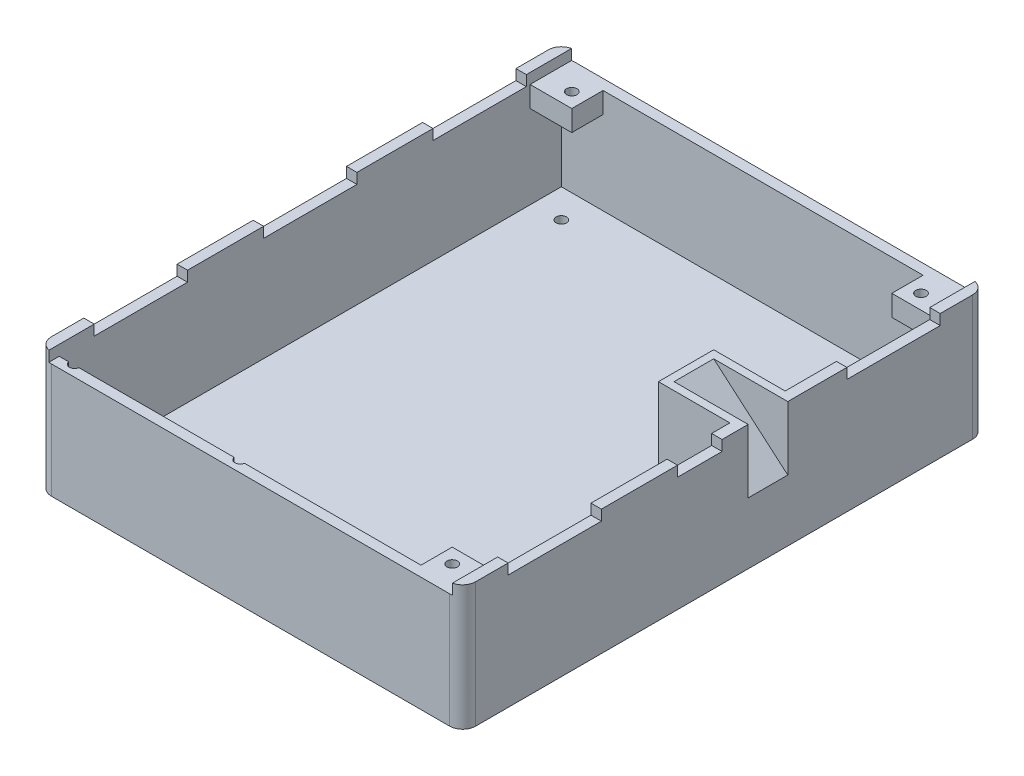
SolidWorks part; units mm, degrees
ref_plane "Front Plane" through (0, 0, 0) normal (0, 0, 1) x (1, 0, 0)
ref_plane "Top Plane" through (0, 0, 0) normal (0, 1, 0) x (1, 0, 0)
ref_plane "Right Plane" through (0, 0, 0) normal (1, 0, 0) x (0, 0, -1)
sketch "Sketch1" plane through (0, 95.465, 0) normal (0, 1, 0) x (1, 0, 0)
  line L9 (159.9807, -123.0664) -> (159.9807, -100.3704) construction
  line L13 (159.9807, -65.3704) -> (159.9807, -47.9349) construction
  line L26 (5.9807, -65.3704) -> (1.9807, -65.3704) construction
  line L27 (1.9807, -65.3704) -> (1.9807, -100.3704) construction
  line L28 (1.9807, -100.3704) -> (5.9807, -100.3704) construction
  line L30 (5.9807, -130.3704) -> (1.9807, -130.3704) construction
  line L31 (1.9807, -130.3704) -> (1.9807, -165.3704) construction
  line L32 (1.9807, -165.3704) -> (5.9807, -165.3704) construction
  line L34 (5.9807, -195.3704) -> (1.9807, -195.3704) construction
  line L35 (1.9807, -195.3704) -> (1.9807, -230.3704) construction
  line L36 (1.9807, -230.3704) -> (5.9807, -230.3704) construction
  line L38 (5.9807, -247.8059) -> (159.9807, -247.8059) construction
  line L39 (159.9807, -247.8059) -> (159.9807, -230.3704) construction
  line L43 (159.9807, -195.3704) -> (159.9807, -165.3704) construction
  line L47 (5.9807, -130.3704) -> (5.9807, -100.3704) construction
  line L48 (5.9807, -195.3704) -> (5.9807, -165.3704) construction
  line L49 (5.9807, -247.8059) -> (5.9807, -230.3704) construction
  line L50 (163.9807, -195.3704) -> (163.9807, -230.3704) construction
  line L51 (163.9807, -149.0664) -> (163.9807, -165.3704) construction
  line L52 (159.9807, -139.0664) -> (159.9807, -149.0664) construction
  line L53 (135.9622, -139.0664) -> (159.9807, -139.0664) construction
  line L54 (135.9622, -123.0664) -> (135.9622, -139.0664) construction
  line L55 (159.9807, -123.0664) -> (135.9622, -123.0664) construction
  line L56 (163.9807, -100.3704) -> (159.9807, -100.3704) construction
  line L57 (159.9807, -65.3704) -> (163.9807, -65.3704) construction
  line L58 (163.9807, -65.3704) -> (163.9807, -100.3704) construction
  line L59 (130.9016, -47.9349) -> (159.9807, -47.9349) construction
  line L60 (5.9807, -47.9349) -> (118.5112, -47.9349) construction
  line L61 (5.9807, -65.3704) -> (5.9807, -47.9349) construction
  line L62 (5.9807, -130.3704) -> (1.9807, -130.3704)
  line L63 (5.9807, -130.3704) -> (5.9807, -100.3704)
  line L64 (1.9807, -100.3704) -> (5.9807, -100.3704)
  line L65 (1.9807, -130.3704) -> (1.9807, -165.3704)
  line L66 (1.9807, -165.3704) -> (5.9807, -165.3704)
  line L67 (5.9807, -195.3704) -> (5.9807, -165.3704)
  line L68 (5.9807, -195.3704) -> (1.9807, -195.3704)
  line L69 (1.9807, -195.3704) -> (1.9807, -230.3704)
  line L70 (1.9807, -230.3704) -> (5.9807, -230.3704)
  line L71 (5.9807, -247.8059) -> (5.9807, -230.3704)
  line L72 (5.9807, -247.8059) -> (159.9807, -247.8059)
  line L73 (159.9807, -247.8059) -> (159.9807, -230.3704)
  line L74 (163.9807, -195.3704) -> (163.9807, -230.3704)
  line L75 (159.9807, -195.3704) -> (159.9807, -165.3704)
  line L76 (163.9807, -149.0664) -> (163.9807, -165.3704)
  line L77 (159.9807, -139.0664) -> (159.9807, -149.0664)
  line L78 (135.9622, -139.0664) -> (159.9807, -139.0664)
  line L79 (135.9622, -123.0664) -> (135.9622, -139.0664)
  line L80 (159.9807, -123.0664) -> (135.9622, -123.0664)
  line L81 (159.9807, -123.0664) -> (159.9807, -100.3704)
  line L82 (163.9807, -100.3704) -> (159.9807, -100.3704)
  line L83 (159.9807, -65.3704) -> (163.9807, -65.3704)
  line L84 (163.9807, -65.3704) -> (163.9807, -100.3704)
  line L85 (159.9807, -65.3704) -> (159.9807, -47.9349)
  line L86 (130.9016, -47.9349) -> (159.9807, -47.9349)
  line L87 (5.9807, -47.9349) -> (118.5112, -47.9349)
  line L88 (5.9807, -65.3704) -> (5.9807, -47.9349)
  line L89 (5.9807, -65.3704) -> (1.9807, -65.3704)
  line L90 (1.9807, -65.3704) -> (1.9807, -100.3704)
  line L91 (163.9807, -230.3704) -> (159.9807, -230.3704) construction
  line L92 (159.9807, -195.3704) -> (163.9807, -195.3704) construction
  line L93 (163.9807, -230.3704) -> (159.9807, -230.3704)
  line L94 (159.9807, -195.3704) -> (163.9807, -195.3704)
  line L95 (163.9807, -165.3704) -> (159.9807, -165.3704) construction
  line L96 (163.9807, -165.3704) -> (159.9807, -165.3704)
  line L97 (159.9807, -149.0664) -> (163.9807, -149.0664) construction
  line L98 (159.9807, -149.0664) -> (163.9807, -149.0664)
  line L99 (5.5807, -47.5349) -> (118.5112, -47.5349)
  line L100 (5.5807, -64.9704) -> (5.5807, -47.5349)
  line L101 (5.5807, -64.9704) -> (1.5807, -64.9704)
  line L102 (1.5807, -64.9704) -> (1.5807, -100.7704)
  line L103 (1.5807, -100.7704) -> (5.5807, -100.7704)
  line L104 (5.5807, -129.9704) -> (5.5807, -100.7704)
  line L105 (5.5807, -129.9704) -> (1.5807, -129.9704)
  line L106 (1.5807, -129.9704) -> (1.5807, -165.7704)
  line L107 (1.5807, -165.7704) -> (5.5807, -165.7704)
  line L108 (5.5807, -194.9704) -> (5.5807, -165.7704)
  line L109 (5.5807, -194.9704) -> (1.5807, -194.9704)
  line L110 (1.5807, -194.9704) -> (1.5807, -230.7704)
  line L111 (1.5807, -230.7704) -> (5.5807, -230.7704)
  line L112 (5.5807, -248.2059) -> (5.5807, -230.7704)
  line L113 (5.5807, -248.2059) -> (160.3807, -248.2059)
  line L114 (160.3807, -248.2059) -> (160.3807, -230.7704)
  line L115 (164.3807, -230.7704) -> (160.3807, -230.7704)
  line L116 (164.3807, -194.9704) -> (164.3807, -230.7704)
  line L117 (160.3807, -194.9704) -> (164.3807, -194.9704)
  line L118 (160.3807, -194.9704) -> (160.3807, -165.7704)
  line L119 (164.3807, -165.7704) -> (160.3807, -165.7704)
  line L120 (164.3807, -148.6664) -> (164.3807, -165.7704)
  line L121 (160.3807, -148.6664) -> (164.3807, -148.6664)
  line L122 (160.3807, -138.6664) -> (160.3807, -148.6664)
  line L123 (136.3622, -138.6664) -> (160.3807, -138.6664)
  line L124 (136.3622, -123.4664) -> (136.3622, -138.6664)
  line L125 (160.3807, -123.4664) -> (136.3622, -123.4664)
  line L126 (160.3807, -123.4664) -> (160.3807, -100.7704)
  line L127 (164.3807, -100.7704) -> (160.3807, -100.7704)
  line L128 (164.3807, -64.9704) -> (164.3807, -100.7704)
  line L129 (160.3807, -64.9704) -> (164.3807, -64.9704)
  line L130 (160.3807, -64.9704) -> (160.3807, -47.5349)
  line L131 (130.9016, -47.5349) -> (160.3807, -47.5349)
  line L133 (164.3807, -248.2059) -> (1.5807, -248.2059)
  line L134 (164.3807, -248.2059) -> (164.3807, -47.5349)
  line L135 (164.3807, -47.5349) -> (1.5807, -47.5349)
  line L136 (1.5807, -248.2059) -> (1.5807, -47.5349)
  dimension "D1" = 0.4
extrude "Boss-Extrude2" add sketch "Sketch1" against normal blind 4 contours L136 L101 L100 L135 | L136 L105 L104 L103 | L136 L109 L108 L107 | L136 L133 L112 L111 | L133 L134 L115 L114 | L117 L134 L119 L118 | L121 L134 L127 L126 L125 L124 L123 L122 | L134 L135 L130 L129 region at (3.5807, 95.465, 56.2527) region at (162.3807, 95.465, 56.2527) region at (3.5807, 95.465, 115.3704) region at (3.5807, 95.465, 180.3704) region at (153.1929, 95.465, 128.8817) region at (3.5807, 95.465, 239.4882) region at (162.3807, 95.465, 180.3704) region at (162.3807, 95.465, 239.4882)
sketch "Sketch2" plane through (0, 95.465, 0) normal (0, 1, 0) x (1, 0, 0)
  line L1 (136.3622, -123.4664) -> (164.3807, -123.4664)
  line L2 (136.3622, -123.4664) -> (136.3622, -138.6664)
  line L3 (136.3622, -138.6664) -> (164.3807, -138.6664)
  line L4 (164.3807, -123.4664) -> (164.3807, -138.6664)
  line L8 (160.3807, -148.6664) -> (164.3807, -148.6664)
  line L9 (164.3807, -148.6664) -> (164.3807, -100.7704)
  line L10 (164.3807, -100.7704) -> (160.3807, -100.7704)
  line L11 (160.3807, -100.7704) -> (160.3807, -123.4664)
  line L12 (160.3807, -123.4664) -> (136.3622, -123.4664)
  line L13 (136.3622, -123.4664) -> (136.3622, -138.6664)
  line L14 (136.3622, -138.6664) -> (160.3807, -138.6664)
  line L15 (160.3807, -138.6664) -> (160.3807, -148.6664)
  line L16 (160.3807, -148.6664) -> (164.3807, -148.6664)
  line L17 (164.3807, -148.6664) -> (164.3807, -100.7704)
  line L18 (164.3807, -100.7704) -> (160.3807, -100.7704)
  line L19 (160.3807, -100.7704) -> (160.3807, -123.4664)
  line L20 (160.3807, -123.4664) -> (136.3622, -123.4664)
  line L21 (136.3622, -123.4664) -> (136.3622, -138.6664)
  line L22 (136.3622, -138.6664) -> (160.3807, -138.6664)
  line L23 (160.3807, -138.6664) -> (160.3807, -148.6664)
  line M10 (164.3807, -148.6664) -> (164.3807, -100.7704)
  line M13 (160.3807, -123.4664) -> (136.3622, -123.4664)
  line M14 (136.3622, -123.4664) -> (136.3622, -138.6664)
  line M15 (136.3622, -138.6664) -> (160.3807, -138.6664)
  dimension "D1" = 0
extrude "Cut-Extrude1" cut sketch "Sketch2" against normal blind 4 contours L3 L1 M15 M10 M13 M14 region at (150.3715, 95.465, 131.0664)
sketch "Sketch3" plane through (0, 91.465, 0) normal (0, -1, 0) x (1, 0, 0)
  line L0 (160.3807, 51.5349) -> (160.3807, 244.2059)
  line L1 (164.3807, 47.5349) -> (1.5807, 47.5349)
  line L2 (164.3807, 47.5349) -> (164.3807, 248.2059)
  line L3 (164.3807, 248.2059) -> (1.5807, 248.2059)
  line L4 (1.5807, 47.5349) -> (1.5807, 248.2059)
  line L5 (160.3807, 244.2059) -> (5.5807, 244.2059)
  line L6 (5.5807, 51.5349) -> (5.5807, 244.2059)
  line L7 (160.3807, 51.5349) -> (5.5807, 51.5349)
  dimension "D1" = 4
extrude "Boss-Extrude3" add sketch "Sketch3" along normal blind 40
sketch "Sketch4" plane through (0, 51.465, 0) normal (0, -1, 0) x (1, 0, 0)
  line L1 (1.5807, 47.5349) -> (164.3807, 47.5349)
  line L2 (1.5807, 47.5349) -> (1.5807, 248.2059)
  line L3 (1.5807, 248.2059) -> (164.3807, 248.2059)
  line L4 (164.3807, 47.5349) -> (164.3807, 248.2059)
extrude "Boss-Extrude4" add sketch "Sketch4" along normal blind 4
fillet "Fillet1" radius 5 1 edges at (1.5807, 71.465, 248.2059)
fillet "Fillet2" radius 5 1 edges at (164.3807, 71.465, 248.2059)
fillet "Fillet3" radius 5 1 edges at (164.3807, 71.465, 47.5349)
fillet "Fillet4" radius 5 1 edges at (1.5807, 71.465, 47.5349)
sketch "Sketch5" plane through (0, 47.465, 0) normal (0, -1, 0) x (1, 0, 0)
  line L0 (164.3807, 52.5349) -> (164.3807, 243.2059) construction
  line L1 (164.3807, 47.5349) -> (149.3807, 47.5349)
  line L2 (164.3807, 47.5349) -> (164.3807, 62.5349)
  line L3 (164.3807, 62.5349) -> (149.3807, 62.5349)
  line L4 (1.5807, 243.2059) -> (1.5807, 52.5349)
  line L5 (6.5807, 47.5349) -> (159.3807, 47.5349)
  line L6 (164.3807, 52.5349) -> (164.3807, 243.2059)
  line L7 (159.3807, 248.2059) -> (6.5807, 248.2059)
  line L8 (1.5807, 243.2059) -> (1.5807, 52.5349)
  line L9 (6.5807, 47.5349) -> (159.3807, 47.5349)
  line L10 (164.3807, 52.5349) -> (164.3807, 243.2059)
  line L11 (159.3807, 248.2059) -> (6.5807, 248.2059)
  line L12 (149.3807, 47.5349) -> (149.3807, 62.5349)
  line L13 (1.5807, 47.5349) -> (16.5807, 47.5349)
  line L14 (1.5807, 47.5349) -> (1.5807, 62.5349)
  line L15 (1.5807, 62.5349) -> (16.5807, 62.5349)
  line L16 (16.5807, 47.5349) -> (16.5807, 62.5349)
  line L17 (1.5807, 248.2059) -> (16.5807, 248.2059)
  line L18 (1.5807, 248.2059) -> (1.5807, 233.2059)
  line L19 (1.5807, 233.2059) -> (16.5807, 233.2059)
  line L20 (16.5807, 248.2059) -> (16.5807, 233.2059)
  line L21 (164.3807, 248.2059) -> (149.3807, 248.2059)
  line L22 (164.3807, 248.2059) -> (164.3807, 233.2059)
  line L23 (164.3807, 233.2059) -> (149.3807, 233.2059)
  line L24 (149.3807, 248.2059) -> (149.3807, 233.2059)
  line L25 (6.5807, 47.5349) -> (159.3807, 47.5349) construction
  line L26 (1.5807, 243.2059) -> (1.5807, 52.5349) construction
  line L27 (159.3807, 248.2059) -> (6.5807, 248.2059) construction
  circle A0 centre (149.3807, 62.5349) radius 2
  circle A1 centre (16.5807, 62.5349) radius 2
  circle A2 centre (149.3807, 233.2059) radius 2
  circle A3 centre (16.5807, 233.2059) radius 2
  arc A4 (1.5807, 52.5349) -> (6.5807, 47.5349) centre (6.5807, 52.5349) ccw
  arc A5 (159.3807, 47.5349) -> (164.3807, 52.5349) centre (159.3807, 52.5349) ccw
  arc A6 (164.3807, 243.2059) -> (159.3807, 248.2059) centre (159.3807, 243.2059) ccw
  arc A7 (6.5807, 248.2059) -> (1.5807, 243.2059) centre (6.5807, 243.2059) ccw
  arc A8 (1.5807, 52.5349) -> (6.5807, 47.5349) centre (6.5807, 52.5349) ccw
  arc A9 (159.3807, 47.5349) -> (164.3807, 52.5349) centre (159.3807, 52.5349) ccw
  arc A10 (164.3807, 243.2059) -> (159.3807, 248.2059) centre (159.3807, 243.2059) ccw
  arc A11 (6.5807, 248.2059) -> (1.5807, 243.2059) centre (6.5807, 243.2059) ccw
  dimension "D10" = 4
  dimension "D11" = 4
  dimension "D12" = 4
  dimension "D13" = 4
  dimension "D2" = 15
  dimension "D3" = 15
  dimension "D4" = 15
  dimension "D5" = 15
  dimension "D6" = 15
  dimension "D7" = 15
  dimension "D8" = 15
  dimension "D9" = 15
  dimension "D1" = 0
extrude "Cut-Extrude2" cut sketch "Sketch5" against normal up to surface (4 mm away) contours A0 | A1 | A3 | A2 up to face at (82.9807, 51.465, 147.8704)
sketch "Sketch6" plane through (0, 91.465, 0) normal (0, 1, 0) x (1, 0, 0)
  line L0 (6.5807, -47.5349) -> (5.5807, -47.5349)
  line L1 (5.5807, -47.636) -> (5.5807, -47.5349)
  line L3 (5.5807, -47.5349) -> (21.5807, -47.5349)
  line L4 (5.5807, -47.5349) -> (5.5807, -63.5349)
  line L5 (5.5807, -63.5349) -> (21.5807, -63.5349)
  line L6 (159.3807, -47.5349) -> (6.5807, -47.5349)
  line L7 (5.5807, -47.636) -> (5.5807, -51.5349)
  line L8 (5.5807, -51.5349) -> (160.3807, -51.5349)
  line L9 (160.3807, -51.5349) -> (160.3807, -47.636)
  line L10 (159.3807, -47.5349) -> (6.5807, -47.5349)
  line L11 (5.5807, -47.636) -> (5.5807, -51.5349)
  line L12 (5.5807, -51.5349) -> (160.3807, -51.5349)
  line L13 (160.3807, -51.5349) -> (160.3807, -47.636)
  line L14 (21.5807, -47.5349) -> (21.5807, -63.5349)
  arc A2 (6.5807, -47.5349) -> (5.5807, -47.636) centre (6.5807, -52.5349) ccw
  arc A3 (160.3807, -47.636) -> (159.3807, -47.5349) centre (159.3807, -52.5349) ccw
  arc A4 (6.5807, -47.5349) -> (5.5807, -47.636) centre (6.5807, -52.5349) ccw
  arc A5 (160.3807, -47.636) -> (159.3807, -47.5349) centre (159.3807, -52.5349) ccw
  point P14 (5.5807, -47.636)
  point P15 (5.1598, -47.5349)
  line M14 (5.5807, -51.5349) -> (160.3807, -51.5349)
  dimension "D2" = 16
  dimension "D3" = 16
  dimension "D1" = 0
extrude "Boss-Extrude5" add sketch "Sketch6" against normal blind 8 contours L14 L4 L5 M14 region at (13.5807, 91.465, 57.5349)
sketch "Sketch7" plane through (0, 91.465, 0) normal (0, 1, 0) x (1, 0, 0)
  circle A0 centre (15.9807, -57.9349) radius 2
extrude "Cut-Extrude3" cut sketch "Sketch7" against normal blind 8
ref_plane "Plane1" through (82.9807, 0, 0) normal (-1, 0, 0) x (0, 0, 1)
mirror "Mirror1" about plane through (82.9807, 0, 0) normal (-1, 0, 0) of "Cut-Extrude3", "Boss-Extrude5"
sketch "Sketch8" plane through (0, 91.465, 0) normal (0, 1, 0) x (1, 0, 0)
  line L0 (159.3807, -248.2059) -> (160.3807, -248.2059)
  line L1 (160.3807, -248.2059) -> (160.3807, -248.1049)
  line L3 (160.3807, -248.2059) -> (144.3807, -248.2059)
  line L4 (6.5807, -248.2059) -> (159.3807, -248.2059)
  line L5 (160.3807, -248.1049) -> (160.3807, -244.2059)
  line L6 (160.3807, -244.2059) -> (5.5807, -244.2059)
  line L7 (5.5807, -244.2059) -> (5.5807, -248.1049)
  line L8 (6.5807, -248.2059) -> (159.3807, -248.2059)
  line L9 (160.3807, -248.1049) -> (160.3807, -244.2059)
  line L10 (160.3807, -244.2059) -> (5.5807, -244.2059)
  line L11 (5.5807, -244.2059) -> (5.5807, -248.1049)
  line L12 (160.3807, -248.2059) -> (160.3807, -232.2059)
  line L13 (160.3807, -232.2059) -> (144.3807, -232.2059)
  line L14 (144.3807, -248.2059) -> (144.3807, -232.2059)
  arc A2 (159.3807, -248.2059) -> (160.3807, -248.1049) centre (159.3807, -243.2059) ccw
  arc A3 (5.5807, -248.1049) -> (6.5807, -248.2059) centre (6.5807, -243.2059) ccw
  arc A4 (159.3807, -248.2059) -> (160.3807, -248.1049) centre (159.3807, -243.2059) ccw
  arc A5 (5.5807, -248.1049) -> (6.5807, -248.2059) centre (6.5807, -243.2059) ccw
  line M13 (160.3807, -244.2059) -> (5.5807, -244.2059)
  dimension "D2" = 16
  dimension "D3" = 16
  dimension "D1" = 0
extrude "Boss-Extrude6" add sketch "Sketch8" against normal blind 8 contours L14 L12 L13 M13 region at (152.3807, 91.465, 238.2059)
sketch "Sketch9" plane through (0, 91.465, 0) normal (0, 1, 0) x (1, 0, 0)
  circle A0 centre (149.9807, -237.8059) radius 2
extrude "Cut-Extrude4" cut sketch "Sketch9" against normal blind 8
sketch "Sketch11" plane through (0, 91.465, 0) normal (0, 1, 0) x (1, 0, 0)
  circle A0 centre (11.1807, -243.8759) radius 2
  circle A1 centre (74.6807, -243.8759) radius 2
  dimension "D1" = 4
  dimension "D2" = 4
extrude "Cut-Extrude5" cut sketch "Sketch11" against normal blind 8
sketch "Sketch12" plane through (164.3807, 0, 0) normal (1, 0, 0) x (0, 0, -1)
  line L1 (-123.4664, 95.465) -> (-138.6664, 95.465)
  line L2 (-123.4664, 95.465) -> (-123.4664, 91.465)
  line L3 (-123.4664, 91.465) -> (-138.6664, 91.465)
  line L4 (-138.6664, 95.465) -> (-138.6664, 91.465)
  line L6 (-123.4664, 91.465) -> (-123.4664, 71.045)
  line L7 (-123.4664, 71.045) -> (-138.6664, 71.045)
  line L8 (-138.6664, 91.465) -> (-138.6664, 71.045)
  line M11 (-123.4664, 91.465) -> (-138.6664, 91.465)
  dimension "D1" = 24.42
extrude "Cut-Extrude6" cut sketch "Sketch12" against normal up to surface (4 mm away) contours L8 L7 L6 M11 region at (164.3807, 81.255, 131.0664) up to face at (160.3807, 88.8935, 146.8053)
sketch "Sketch13" plane through (0, 51.465, 0) normal (0, 1, 0) x (1, 0, 0)
  line L0 (160.3807, -123.4664) -> (160.3807, -138.6664) construction
  line L1 (160.3807, -123.4664) -> (160.3807, -138.6664)
  line L2 (160.3807, -120.4664) -> (132.9607, -120.4664)
  line L3 (160.3807, -123.4664) -> (135.9607, -123.4664)
  line L4 (160.3807, -51.5349) -> (5.5807, -51.5349)
  line L5 (5.5807, -51.5349) -> (5.5807, -244.2059)
  line L6 (5.5807, -244.2059) -> (160.3807, -244.2059)
  line L7 (160.3807, -244.2059) -> (160.3807, -51.5349)
  line L8 (160.3807, -51.5349) -> (5.5807, -51.5349)
  line L9 (5.5807, -51.5349) -> (5.5807, -244.2059)
  line L10 (5.5807, -244.2059) -> (160.3807, -244.2059)
  line L11 (160.3807, -244.2059) -> (160.3807, -51.5349)
  line L12 (160.3807, -123.4664) -> (160.3807, -138.6664)
  line L13 (160.3807, -138.6664) -> (135.9607, -138.6664)
  line L14 (135.9607, -123.4664) -> (135.9607, -138.6664)
  line L15 (132.9607, -120.4664) -> (132.9607, -141.6664)
  line L16 (160.3807, -141.6664) -> (132.9607, -141.6664)
  line M16 (160.3807, -244.2059) -> (160.3807, -51.5349)
  dimension "D2" = 24.42
  dimension "D1" = 0
  dimension "D3" = 3
extrude "Boss-Extrude7" add sketch "Sketch13" along normal up to surface (44 mm away) contours L16 L11 L13 L14 L3 L2 L15 M16 region at (148.1707, 51.465, 123.1198) up to face at (162.3807, 95.465, 112.1184)
sketch "Sketch14" plane through (0, 51.465, 0) normal (0, 1, 0) x (1, 0, 0)
  line L4 (135.9607, -123.4664) -> (135.9607, -138.6664)
  line L5 (135.9607, -138.6664) -> (160.3807, -138.6664)
  line L6 (160.3807, -138.6664) -> (160.3807, -123.4664)
  line L7 (160.3807, -123.4664) -> (135.9607, -123.4664)
  line L8 (135.9607, -123.4664) -> (135.9607, -138.6664)
  line L9 (135.9607, -138.6664) -> (160.3807, -138.6664)
  line L10 (160.3807, -138.6664) -> (160.3807, -123.4664)
  line L11 (160.3807, -123.4664) -> (135.9607, -123.4664)
  dimension "D1" = 0
extrude "Boss-Extrude8" add sketch "Sketch14" along normal up to surface (19.58 mm away) up to face at (162.3807, 71.045, 131.0664)
chamfer "Chamfer2" distance 24.42 distance2 28.42 1 edges at (135.9607, 71.045, 131.0664) first distance on face at (135.9607, 83.255, 131.0664)
